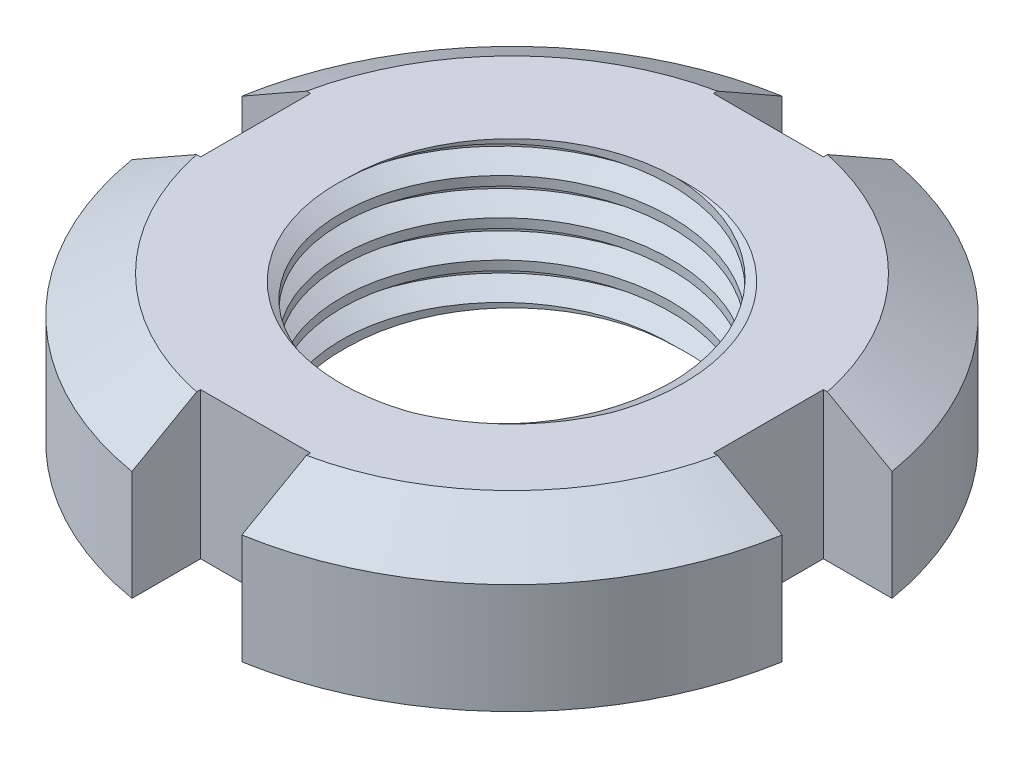
SolidWorks part; units mm, degrees
ref_plane "Front Plane" through (0, 0, 0) normal (0, 0, 1) x (1, 0, 0)
ref_plane "Top Plane" through (0, 0, 0) normal (0, 1, 0) x (1, 0, 0)
ref_plane "Right Plane" through (0, 0, 0) normal (1, 0, 0) x (0, 0, -1)
sketch "Sketch1" plane through (0, 0, 0) normal (0, 1, 0) x (1, 0, 0)
  line L0 (-7, 0) -> (0, 0) construction
  line L1 (-9, 1.5) -> (-7, 1.5)
  line L2 (-9, 1.5) -> (-9, -1.5)
  line L3 (-9, -1.5) -> (-7, -1.5)
  line L4 (-7, 1.5) -> (-7, -1.5)
  line L5 (9, 1.5) -> (7, 1.5)
  line L6 (9, 1.5) -> (9, -1.5)
  line L7 (9, -1.5) -> (7, -1.5)
  line L8 (7, 1.5) -> (7, -1.5)
  line L9 (0, 0) -> (7, 0) construction
  line L10 (1.5, 9) -> (-1.5, 9)
  line L11 (1.5, 9) -> (1.5, 7)
  line L12 (1.5, 7) -> (-1.5, 7)
  line L13 (-1.5, 9) -> (-1.5, 7)
  line L14 (1.5, -9) -> (-1.5, -9)
  line L15 (1.5, -9) -> (1.5, -7)
  line L16 (1.5, -7) -> (-1.5, -7)
  line L17 (-1.5, -9) -> (-1.5, -7)
  line L18 (9, -1.5) -> (9, 1.5)
  line L19 (9, -1.5) -> (7, -1.5)
  line L20 (7, -1.5) -> (7, 1.5)
  line L21 (9, 1.5) -> (7, 1.5)
  line L22 (-9, -1.5) -> (-9, 1.5)
  line L23 (-9, -1.5) -> (-7, -1.5)
  line L24 (-7, -1.5) -> (-7, 1.5)
  line L25 (-9, 1.5) -> (-7, 1.5)
  line L26 (-1.5, -9) -> (1.5, -9)
  line L27 (-1.5, -9) -> (-1.5, -7)
  line L28 (-1.5, -7) -> (1.5, -7)
  line L29 (1.5, -9) -> (1.5, -7)
  line L30 (-1.5, 9) -> (1.5, 9)
  line L31 (-1.5, 9) -> (-1.5, 7)
  line L32 (-1.5, 7) -> (1.5, 7)
  line L33 (1.5, 9) -> (1.5, 7)
  circle A0 centre (0, 0) radius 4.5
  circle A1 centre (0, 0) radius 9
  point P41 (0, 0)
  dimension "D1" = 9
  dimension "D2" = 18
  dimension "D3" = 14
  dimension "D4" = 3
  dimension "D5" = 4
extrude "Boss-Extrude1" add sketch "Sketch1" along normal blind 4 contours L29 A1 L19 L8 L21 L33 L12 L31 L25 L4 L23 L27 L16 A0 region at (-6.1865, 0, -6.1865)
chamfer "Chamfer1" distance 1 angle 60 4 edges at (-6.364, 4, 6.364) (-6.364, 4, -6.364) (6.364, 4, -6.364) (6.364, 4, 6.364) first distance on face at (-5.7755, 2, 5.7755) first distance on face at (-5.7755, 2, -5.7755) first distance on face at (5.7755, 2, -5.7755) first distance on face at (5.7755, 2, 5.7755)
thread "Thread1" pitch 1 method cut profile "Thread Profile1" start angle 0, offset 3, length 10, pitch 1, diameter 9
ref_plane "Plane1" through (-4.5, 7, 0) normal (0, 0, 1) x (-1, 0, 0)
sketch "Thread Profile1" plane through (-4.5, 7, 0) normal (0, 0, 1) x (-1, 0, 0)
  line L0 (0, 0) -> (0, 1) construction
  line L1 (0, 0) -> (0.5413, 0.3125)
  line L2 (0.5413, 0.3125) -> (0.5413, 0.4375)
  line L3 (0.5413, 0.4375) -> (0, 0.75)
  line L4 (0.5413, 0.375) -> (0, 0.375) construction
  line L11 (0, 0) -> (0, 0.75)
  point P2 (0, 0)
  dimension "Pitch" = 1
  dimension "Profile_Angle" = 60
  dimension "Profile_Land" = 0.125
  dimension "Profile_Height" = 0.5413
